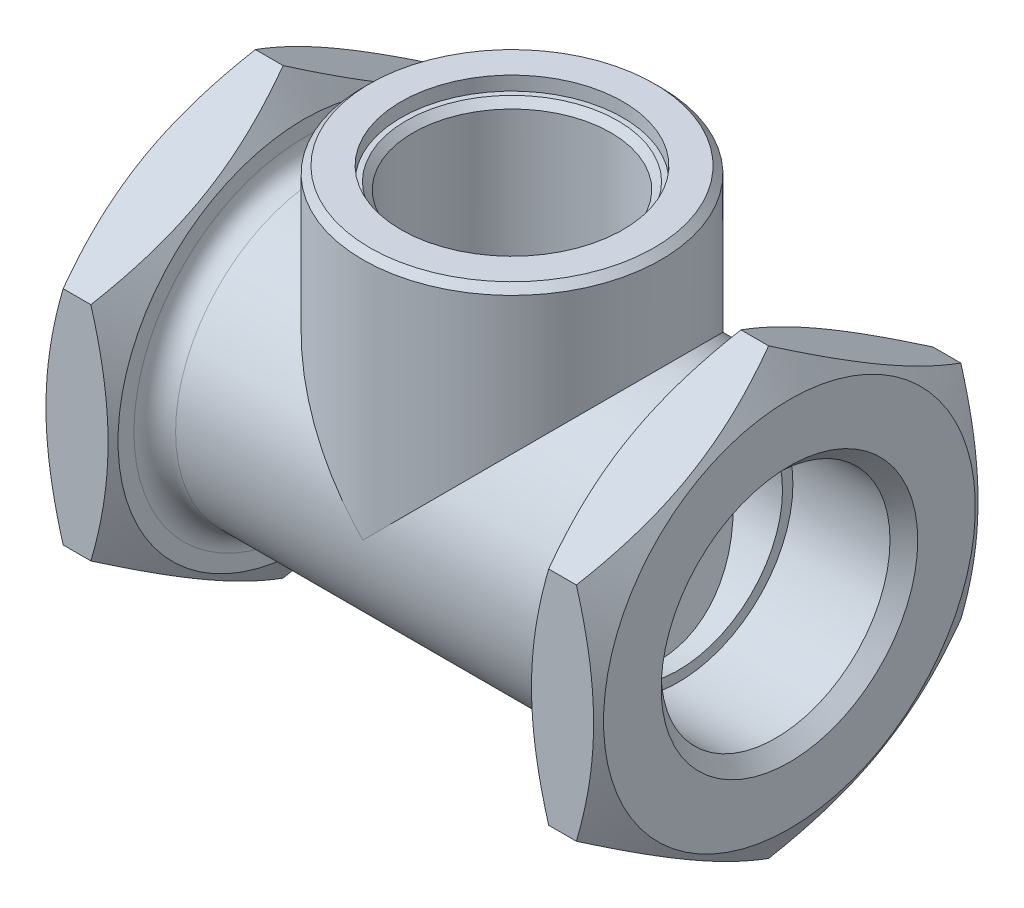
SolidWorks part; units mm, degrees
ref_plane "Front Plane" through (0, 0, 0) normal (0, 0, 1) x (1, 0, 0)
ref_plane "Top Plane" through (0, 0, 0) normal (0, 1, 0) x (1, 0, 0)
ref_plane "Right Plane" through (0, 0, 0) normal (1, 0, 0) x (0, 0, -1)
sketch "Sketch1" plane through (0, 0, 0) normal (1, 0, 0) x (0, 0, -1)
  line L0 (0, 0) -> (0, 32) construction
  line L1 (0, 32) -> (-27.7128, 16)
  line L2 (-27.7128, 16) -> (-27.7128, -16)
  line L3 (-27.7128, -16) -> (0, -32)
  line L4 (0, -32) -> (27.7128, -16)
  line L5 (27.7128, -16) -> (27.7128, 16)
  line L6 (27.7128, 16) -> (0, 32)
  circle A0 centre (0, 0) radius 32 construction
  dimension "D1" = 64
extrude "Boss-Extrude1" add sketch "Sketch1" against normal blind 10
sketch "Sketch2" plane through (-10, 0, 0) normal (-1, 0, 0) x (0, 0, 1)
  circle A0 centre (0, 0) radius 21.5
  circle A1 centre (0, 0) radius 15
  dimension "D1" = 43
  dimension "D2" = 30
extrude "Boss-Extrude2" add sketch "Sketch2" along normal blind 60
sketch "Sketch3" plane through (-70, 0, 0) normal (-1, 0, 0) x (0, 0, 1)
  line L6 (27.7128, 16) -> (0, 32)
  line L7 (27.7128, -16) -> (27.7128, 16)
  line L8 (0, -32) -> (27.7128, -16)
  line L9 (-27.7128, -16) -> (0, -32)
  line L10 (-27.7128, 16) -> (-27.7128, -16)
  line L11 (0, 32) -> (-27.7128, 16)
  line L12 (27.7128, 16) -> (0, 32)
  line L13 (27.7128, -16) -> (27.7128, 16)
  line L14 (0, -32) -> (27.7128, -16)
  line L15 (-27.7128, -16) -> (0, -32)
  line L16 (-27.7128, 16) -> (-27.7128, -16)
  line L17 (0, 32) -> (-27.7128, 16)
  dimension "D1" = 0
extrude "Boss-Extrude3" add sketch "Sketch3" along normal blind 10
ref_plane "Plane1" through (0, 36, 0) normal (0, 1, 0) x (1, 0, 0)
sketch "Sketch5" plane through (0, 36, 0) normal (0, 1, 0) x (1, 0, 0)
  line L0 (0, 0) -> (-40, 0) construction
  circle A0 centre (-40, 0) radius 21.5
  dimension "D2" = 43
  dimension "D1" = 40
extrude "Boss-Extrude4" add sketch "Sketch5" against normal up to surface (36 mm away) up to face at (-70, 0, 21.5)
sketch "Sketch6" plane through (0, 0, 0) normal (0, 0, 1) x (1, 0, 0)
  line L0 (0, 26.8038) -> (0, 32)
  line L1 (0, 32) -> (0, 16) construction
  line L2 (0, 32) -> (-3, 32)
  line L3 (-10, 32) -> (0, 32) construction
  line L4 (-3, 32) -> (0, 26.8038)
  line L5 (-10, 26.8038) -> (-10, 32)
  line L6 (-10, 32) -> (-10, 16) construction
  line L7 (-10, 32) -> (-7, 32)
  line L8 (-7, 32) -> (-10, 26.8038)
  line L9 (-40, 36) -> (-40, -28.5305) construction
  line L10 (-18.5, 36) -> (-61.5, 36) construction
  line L11 (-80, 0) -> (0, 0) construction
  line L12 (-80, -16) -> (-80, 16) construction
  line L13 (-73, 32) -> (-70, 26.8038)
  line L14 (-70, 32) -> (-73, 32)
  line L15 (-70, 26.8038) -> (-70, 32)
  line L16 (-77, 32) -> (-80, 26.8038)
  line L17 (-80, 32) -> (-77, 32)
  line L18 (-80, 26.8038) -> (-80, 32)
  dimension "D1" = 30
  dimension "D2" = 3
  dimension "D3" = 30
  dimension "D4" = 3
revolve "Cut-Revolve1" cut sketch "Sketch6" angle 360 about L11
fillet "Fillet1" radius 3 2 edges at (-10, 0, -21.5) (-70, 0, 21.5)
sketch "Sketch7" plane through (0, 0, 0) normal (1, 0, 0) x (0, 0, -1)
  circle A0 centre (0, 0) radius 15
  dimension "D1" = 30
extrude "Cut-Extrude1" cut sketch "Sketch7" against normal through all
sketch "Sketch8" plane through (0, 36, 0) normal (0, 1, 0) x (1, 0, 0)
  circle A0 centre (-40, 0) radius 16
  dimension "D1" = 32
extrude "Cut-Extrude2" cut sketch "Sketch8" against normal blind 2
sketch "Sketch9" plane through (0, 34, 0) normal (0, 1, 0) x (1, 0, 0)
  circle A0 centre (-40, 0) radius 14.25
  dimension "D1" = 28.5
extrude "Cut-Extrude3" cut sketch "Sketch9" against normal blind 31
sketch "Sketch10" plane through (0, 0, 0) normal (0, 1, 0) x (1, 0, 0)
  line L0 (0, 0) -> (-40, 0) construction
  line L1 (0, -26.8038) -> (0, 26.8038) construction
  line L3 (-25, -17.5) -> (-55, -17.5)
  line L4 (-25, -17.5) -> (-25, 17.5)
  line L5 (-25, 17.5) -> (-55, 17.5)
  line L6 (-55, -17.5) -> (-55, 17.5)
  line L7 (-25, -17.5) -> (-55, 17.5) construction
  line L8 (-25, 17.5) -> (-55, -17.5) construction
  dimension "D1" = 40
  dimension "D2" = 30
  dimension "D3" = 35
extrude "Boss-Extrude5" add sketch "Sketch10" along normal mid plane 5
sketch "Sketch11" plane through (0, 2.5, 0) normal (0, 1, 0) x (1, 0, 0)
  circle A0 centre (-40, 0) radius 10
  dimension "D1" = 20
extrude "Cut-Extrude4" cut sketch "Sketch11" against normal blind 5
sketch "Sketch12" plane through (0, 0, 0) normal (0, 0, 1) x (1, 0, 0)
  line L0 (-28.1801, -2.5) -> (-23.6305, -15)
  line L1 (-55, -2.5) -> (-25, -2.5) construction
  line L2 (-80, -15) -> (0, -15) construction
  line L3 (-23.6305, -15) -> (-18.6305, -15)
  line L4 (-18.6305, -15) -> (-25, 2.5)
  line L5 (-25, 2.5) -> (-28.1801, -2.5)
  dimension "D1" = 5
  dimension "D2" = 110
extrude "Boss-Extrude6" add sketch "Sketch12" along normal mid plane 30
fillet "Fillet2" radius 3 2 edges at (-28.1801, -2.5, 0) (-25, 2.5, 0)
sketch "Sketch13" plane through (0, -2.5, 0) normal (0, -1, 0) x (1, 0, 0)
  line L0 (-40, 21) -> (-40, 15)
  line L1 (-40, -15) -> (-40, -21)
  arc A0 (-40, 15) -> (-40, -15) centre (-40, 0) ccw
  arc A1 (-40, 21) -> (-40, -21) centre (-40, 0) ccw
  dimension "D1" = 42
  dimension "D2" = 30
extrude "Boss-Extrude7" add sketch "Sketch13" against normal blind 20
sketch "Sketch14" plane through (0, 0, 0) normal (1, 0, 0) x (0, 0, -1)
  circle A0 centre (0, 0) radius 16.5
  dimension "D1" = 33
extrude "Cut-Extrude5" cut sketch "Sketch14" against normal blind 16
sketch "Sketch15" plane through (-80, 0, 0) normal (-1, 0, 0) x (0, 0, 1)
  circle A0 centre (0, 0) radius 16.5
  dimension "D1" = 33
extrude "Cut-Extrude6" cut sketch "Sketch15" against normal blind 16
chamfer "Chamfer1" distance 2 angle 45 2 edges at (0, 0, -16.5) (-80, 0, 16.5)
chamfer "Chamfer3" distance 1 angle 45 2 edges at (-40, 34, 14.25) (-40, 36, 21.5)
